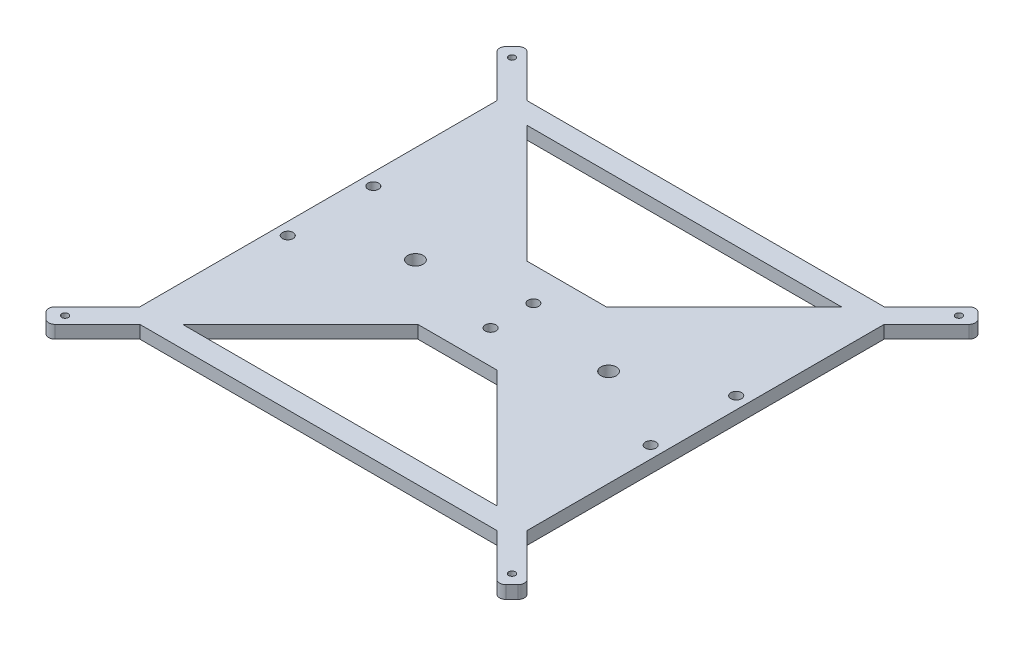
SolidWorks part; units mm, degrees
ref_plane "Front Plane" through (0, 0, 0) normal (0, 0, 1) x (1, 0, 0)
ref_plane "Top Plane" through (0, 0, 0) normal (0, 1, 0) x (1, 0, 0)
ref_plane "Right Plane" through (0, 0, 0) normal (1, 0, 0) x (0, 0, -1)
sketch "Sketch1" plane through (0, 0, 0) normal (0, 1, 0) x (1, 0, 0)
  line L0 (-83.5, 90.5711) -> (83.5, 90.5711)
  line L1 (-104.5, -104.5) -> (104.5, -104.5) construction
  line L2 (-104.5, -104.5) -> (-104.5, 104.5) construction
  line L3 (-104.5, 104.5) -> (104.5, 104.5) construction
  line L4 (104.5, -104.5) -> (104.5, 104.5) construction
  line L5 (-104.5, -104.5) -> (104.5, 104.5) construction
  line L6 (-104.5, 104.5) -> (104.5, -104.5) construction
  line L7 (83.5, 90.5711) -> (103.299, 110.3701)
  line L8 (107.5416, 110.3701) -> (110.3701, 107.5416)
  line L9 (110.3701, 103.299) -> (90.5711, 83.5)
  line L10 (90.5711, 83.5) -> (90.5711, -83.5)
  line L11 (90.5711, -83.5) -> (110.3701, -103.299)
  line L12 (110.3701, -107.5416) -> (107.5416, -110.3701)
  line L13 (103.299, -110.3701) -> (83.5, -90.5711)
  line L14 (83.5, -90.5711) -> (-83.5, -90.5711)
  line L15 (-83.5, -90.5711) -> (-103.299, -110.3701)
  line L16 (-107.5416, -110.3701) -> (-110.3701, -107.5416)
  line L17 (-110.3701, -103.299) -> (-90.5711, -83.5)
  line L18 (-90.5711, -83.5) -> (-90.5711, 83.5)
  line L19 (-90.5711, 83.5) -> (-110.3701, 103.299)
  line L20 (-110.3701, 107.5416) -> (-107.5416, 110.3701)
  line L21 (-103.299, 110.3701) -> (-83.5, 90.5711)
  circle A0 centre (-104.5, 104.5) radius 1.55
  circle A1 centre (104.5, 104.5) radius 1.55
  circle A2 centre (104.5, -104.5) radius 1.55
  circle A3 centre (-104.5, -104.5) radius 1.55
  arc A4 (-110.3701, -107.5416) -> (-110.3701, -103.299) centre (-108.2487, -105.4203) cw
  arc A5 (-103.299, -110.3701) -> (-107.5416, -110.3701) centre (-105.4203, -108.2487) cw
  arc A6 (107.5416, -110.3701) -> (103.299, -110.3701) centre (105.4203, -108.2487) cw
  arc A7 (110.3701, -103.299) -> (110.3701, -107.5416) centre (108.2487, -105.4203) cw
  arc A8 (110.3701, 107.5416) -> (110.3701, 103.299) centre (108.2487, 105.4203) cw
  arc A9 (103.299, 110.3701) -> (107.5416, 110.3701) centre (105.4203, 108.2487) cw
  arc A10 (-107.5416, 110.3701) -> (-103.299, 110.3701) centre (-105.4203, 108.2487) cw
  arc A11 (-110.3701, 103.299) -> (-110.3701, 107.5416) centre (-108.2487, 105.4203) cw
  point P0 (0, 0)
  point P10 (0, 90.5711)
  point P27 (-90.5711, 0)
  point P42 (-105.4203, 112.4914)
  point P45 (-112.4914, 105.4203)
  dimension "D2" = 3.1
  dimension "D1" = 209
  dimension "D3" = 31
  dimension "D4" = 167
  dimension "D5" = 10
extrude "Boss-Extrude2" add sketch "Sketch1" along normal blind 6 contours L0 L7 A9 L8 A8 L9 L10 L11 A7 L12 A6 L13 L14 L15 A5 L16 A4 L17 L18 L19 A11 L20 A10 L21
extrude "Cut-Extrude4" cut sketch "Sketch1<6>" along normal blind 6 contours A3 | A0 | A1 | A2
sketch "Sketch1<6>" plane through (0, 0, 0) normal (0, 1, 0) x (1, 0, 0) same geometry as "Sketch1"
sketch "Sketch2" plane through (0, 6, 0) normal (0, 1, 0) x (1, 0, 0)
  line L0 (-45.15, 20) -> (-45.15, -20) construction
  line L1 (-97.75, 32.75) -> (-32.25, 32.75) construction
  line L2 (-97.75, 32.75) -> (-97.75, -32.75) construction
  line L3 (-97.75, -32.75) -> (-32.25, -32.75) construction
  line L4 (-32.25, 32.75) -> (-32.25, -32.75) construction
  line L5 (-97.75, 32.75) -> (-32.25, -32.75) construction
  line L6 (-97.75, -32.75) -> (-32.25, 32.75) construction
  line L39 (0, 0) -> (0, 52.2338) construction
  circle A0 centre (-84.85, 20) radius 2.5
  circle A1 centre (-84.85, -20) radius 2.5
  circle A2 centre (45.15, 0) radius 3.6
  circle A3 centre (84.85, -20) radius 2.5
  circle A4 centre (-45.15, 0) radius 3.6
  circle A5 centre (84.85, 20) radius 2.5
  point P0 (-65, 0)
  point P15 (-45.15, 0)
  dimension "D2" = 5
  dimension "D4" = 7.2
  dimension "D1" = 65.5
  dimension "D3" = 12.75
  dimension "D9" = 12.9
  dimension "D10" = 12.75
  dimension "D11" = 12.9
  dimension "D18" = 65
extrude "Cut-Extrude5" cut sketch "Sketch2" against normal blind 6
sketch "Sketch3" plane through (0, 6, 0) normal (0, 1, 0) x (1, 0, 0)
  line L0 (0, 10) -> (0, 0) construction
  line L1 (0, 0) -> (0, -10) construction
  circle A0 centre (0, 10) radius 2.5
  circle A1 centre (0, -10) radius 2.5
  dimension "D1" = 5
  dimension "D2" = 20
extrude "Cut-Extrude6" cut sketch "Sketch3" against normal blind 6
sketch "Sketch4" plane through (0, 6, 0) normal (0, 1, 0) x (1, 0, 0)
  line L0 (-73.5, 80.5711) -> (73.5, 80.5711)
  line L1 (73.5, 80.5711) -> (18.5, 25.5711)
  line L2 (18.5, 25.5711) -> (-18.5, 25.5711)
  line L3 (-18.5, 25.5711) -> (-73.5, 80.5711)
  line L6 (-83.5, 90.5711) -> (83.5, 90.5711) construction
  line L7 (0, 0) -> (28.9227, 0) construction
  line L8 (73.5, -80.5711) -> (18.5, -25.5711)
  line L9 (-73.5, -80.5711) -> (73.5, -80.5711)
  line L10 (-18.5, -25.5711) -> (-73.5, -80.5711)
  line L11 (18.5, -25.5711) -> (-18.5, -25.5711)
  line L14 (-103.299, 110.3701) -> (-83.5, 90.5711) construction
  line L17 (83.5, 90.5711) -> (103.299, 110.3701) construction
  dimension "D1" = 55
  dimension "D2" = 10
extrude "Cut-Extrude7" cut sketch "Sketch4" against normal blind 6
